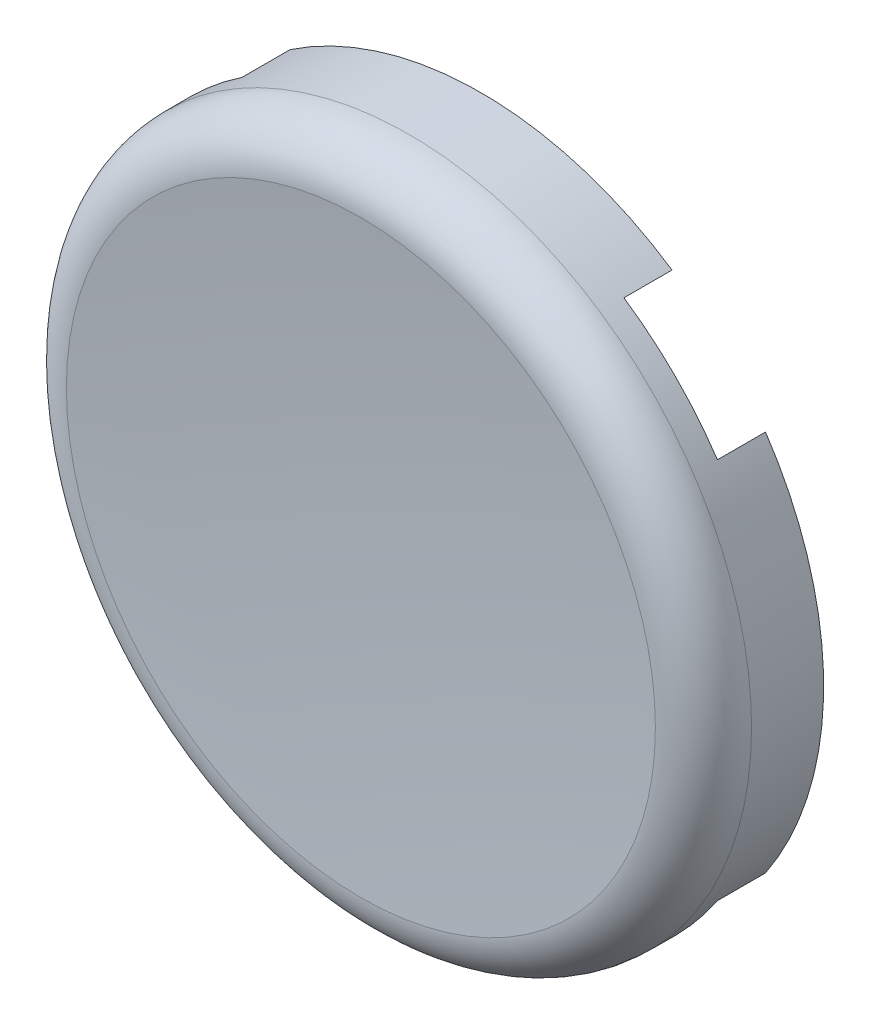
SolidWorks part; units mm, degrees
ref_plane "Front Plane" through (0, 0, 0) normal (0, 0, 1) x (1, 0, 0)
ref_plane "Top Plane" through (0, 0, 0) normal (0, 1, 0) x (1, 0, 0)
ref_plane "Right Plane" through (0, 0, 0) normal (1, 0, 0) x (0, 0, -1)
sketch "Sketch1" plane through (0, 0, 0) normal (0, 1, 0) x (1, 0, 0)
  line L1 (0, 0) -> (14.25, 0)
  line L2 (0, 0) -> (0, -5)
  line L3 (0, -5) -> (14.25, -5)
  line L4 (14.25, 0) -> (14.25, -5)
  line L5 (0, 0) -> (2.8, 0)
  line L6 (0, 0) -> (0, 1.2)
  line L7 (0, 1.2) -> (2.8, 1.2)
  line L8 (2.8, 0) -> (2.8, 1.2)
  line L9 (2.8, 0) -> (12.75, 0)
  line L10 (2.8, 0) -> (2.8, -3.6)
  line L11 (2.8, -3.6) -> (12.75, -3.6)
  line L12 (12.75, 0) -> (12.75, -3.6)
  line L13 (0, -5) -> (-14.25, -5)
  line L15 (2.8, -3.6) -> (12.75, -3.6)
  line L16 (2.8, -3.6) -> (2.8, -3.1)
  line L17 (2.8, -3.1) -> (12.75, -3.1)
  line L18 (12.75, -3.6) -> (12.75, -3.1)
  circle A0 centre (0, -154.8125) radius 150.3125
  point P11 (0, -4.5)
  point P14 (-12.25, -5)
  point P22 (12.25, -5)
  dimension "D1" = 14.25
  dimension "D2" = 6.2
  dimension "D3" = 2.8
  dimension "D4" = 5
  dimension "D5" = 1.4
  dimension "D6" = 1.5
  dimension "D7" = 0.5
  dimension "D8" = 14.25
  dimension "D9" = 2
  dimension "D11" = 0.5
  dimension "D10" = 2
revolve "Revolve1" add sketch "Sketch1" angle 360 about L2 region at (1.4, 0, -0.6) region at (1.4, 0, 0.151) region at (7.775, 0, 3.35)
sketch "Sketch2" plane through (0, 0, 0) normal (0, 0, 1) x (1, 0, 0)
  line L0 (8.1317, 12.0208) -> (12.0208, 8.1317)
  line L1 (10.748, 10.748) -> (-10.748, 10.748)
  line L2 (10.748, 10.748) -> (10.748, -10.748)
  line L3 (10.748, -10.748) -> (-10.748, -10.748)
  line L4 (-10.748, 10.748) -> (-10.748, -10.748)
  line L5 (12.0208, 8.1317) -> (-8.1317, -12.0208)
  line L6 (-8.1317, -12.0208) -> (-12.0208, -8.1317)
  line L7 (-12.0208, -8.1317) -> (8.1317, 12.0208)
  line L8 (-8.1317, 12.0208) -> (12.0208, -8.1317)
  line L9 (12.0208, -8.1317) -> (8.1317, -12.0208)
  line L10 (8.1317, -12.0208) -> (-12.0208, 8.1317)
  line L11 (-12.0208, 8.1317) -> (-8.1317, 12.0208)
  circle A0 centre (0, 0) radius 12.75
  circle A1 centre (0, 0) radius 12.75 construction
  circle A3 centre (0, 0) radius 14.25 construction
  point P4 (0, 10.748)
  point P6 (10.748, 0)
  point P12 (10.748, 6.8589)
  point P13 (6.8589, 10.748)
  point P14 (-10.748, 6.8589)
  point P15 (-10.748, -6.8589)
  point P16 (-6.8589, 10.748)
  point P17 (-6.8589, -10.748)
  point P18 (6.8589, -10.748)
  point P19 (10.748, -6.8589)
  dimension "D1" = 5.5
extrude "Cut-Extrude2" cut sketch "Sketch2" along normal offset from surface (2 mm away) 2 contours A0 L2 L0 L1 | L7 L1 L0 | L5 L0 L2 | L9 L8 L2 | A0 L3 L9 L2 | L10 L9 L3 | L6 L5 L3 | A0 L4 L6 L3 | L7 L6 L4 | L11 L10 L4 | A0 L1 L11 L4 | L11 L1 L8 region at (8.1317, 11.1722, 0) region at (9.4256, 9.4256, 0) region at (11.1722, 8.1317, 0) region at (-9.4256, 9.4256, 0) region at (-8.1317, 11.1722, 0) region at (-11.1722, 8.1317, 0) region at (11.1722, -8.1317, 0) region at (9.4256, -9.4256, 0) region at (-9.4256, -9.4256, 0) region at (-11.1722, -8.1317, 0) region at (8.1317, -11.1722, 0) region at (-8.1317, -11.1722, 0) up to face at (-14.25, 0, 0)
sketch "Sketch3" plane through (0, 0, -1.2) normal (0, 0, -1) x (-1, 0, 0)
  line L1 (-2.05, 0.585) -> (2.05, 0.585)
  line L2 (-2.05, 0.585) -> (-2.05, -0.585)
  line L3 (-2.05, -0.585) -> (2.05, -0.585)
  line L4 (2.05, 0.585) -> (2.05, -0.585)
  line L5 (-0.585, 2.05) -> (0.585, 2.05)
  line L6 (-0.585, 2.05) -> (-0.585, -2.05)
  line L7 (-0.585, -2.05) -> (0.585, -2.05)
  line L8 (0.585, 2.05) -> (0.585, -2.05)
  point P8 (0.585, 0)
  point P10 (2.05, 0)
  point P11 (0, 2.05)
  point P12 (0, 0.585)
  dimension "D1" = 1.17
  dimension "D2" = 4.1
extrude "Cut-Extrude3" cut sketch "Sketch3" against normal up to surface (4.3 mm away) contours L8 L5 L6 L1 | L8 L1 L6 L3 | L8 L3 L6 L7 | L6 L1 L2 L3 | L1 L8 L3 L4 region at (1.3175, 0, -1.2) region at (0, 1.3175, -1.2) region at (0, 0, -1.2) region at (-1.3175, 0, -1.2) region at (0, -1.3175, -1.2) up to face at (-12.75, 0, 3.1)
fillet "Fillet1" radius 0.3 4 edges at (-0.585, -0.585, 0.95) (0.585, -0.585, 0.95) (-0.585, 0.585, 0.95) (0.585, 0.585, 0.95)
fillet "Fillet2" radius 1 1 edges at (-12.75, 0, 3.1)
fillet "Fillet3" radius 2 1 edges at (-14.25, 0, 5)
